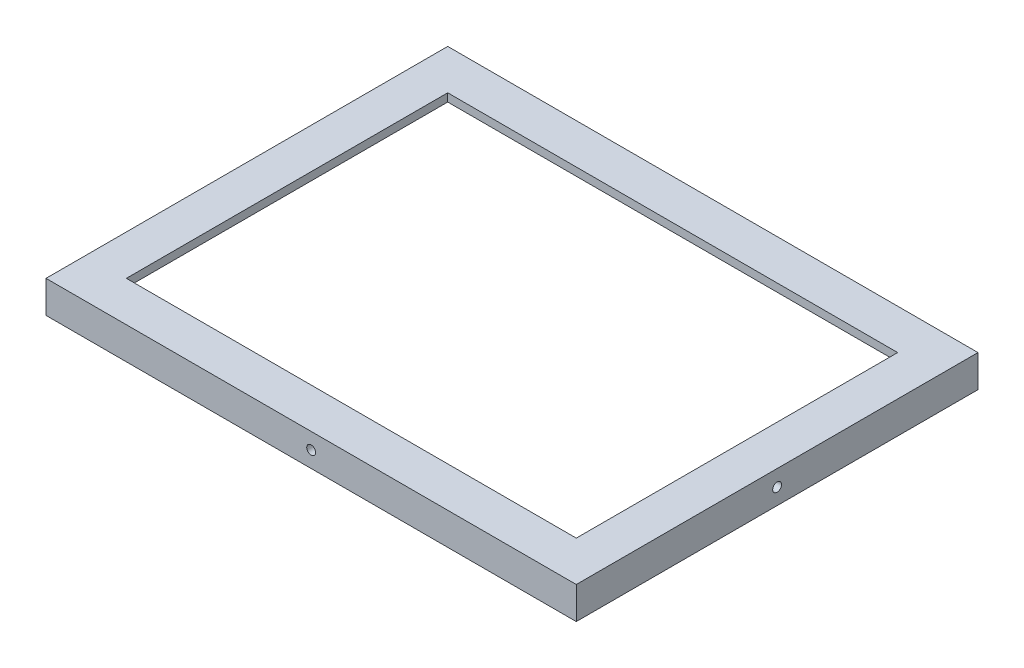
SolidWorks part; units mm, degrees
ref_plane "Front Plane" through (0, 0, 0) normal (0, 0, 1) x (1, 0, 0)
ref_plane "Top Plane" through (0, 0, 0) normal (0, 1, 0) x (1, 0, 0)
ref_plane "Right Plane" through (0, 0, 0) normal (1, 0, 0) x (0, 0, -1)
sketch "Sketch1" plane through (0, 9.525, 0) normal (0, 1, 0) x (1, 0, 0)
  line L12 (261.9455, 40.3596) -> (84.1455, 40.3596)
  line L13 (84.1455, 40.3596) -> (84.1455, -86.6404)
  line L14 (84.1455, -86.6404) -> (261.9455, -86.6404)
  line L15 (261.9455, -86.6404) -> (261.9455, 40.3596)
  line L16 (277.8205, 56.2346) -> (68.2705, 56.2346)
  line L17 (277.8205, -102.5154) -> (277.8205, 56.2346)
  line L18 (68.2705, -102.5154) -> (277.8205, -102.5154)
  line L19 (68.2705, 56.2346) -> (68.2705, -102.5154)
  line L20 (277.8205, 56.2346) -> (68.2705, 56.2346)
  line L21 (277.8205, -102.5154) -> (277.8205, 56.2346)
  line L22 (68.2705, -102.5154) -> (277.8205, -102.5154)
  line L23 (68.2705, 56.2346) -> (68.2705, -102.5154)
  dimension "D1" = 3.175
extrude "FrontFace" add sketch "Sketch1" along normal blind 3.175
sketch "Sketch3" plane through (0, 9.525, 0) normal (0, -1, 0) x (1, 0, 0)
  line L4 (277.8205, -56.2346) -> (277.8205, 102.5154)
  line L5 (277.8205, 102.5154) -> (68.2705, 102.5154)
  line L6 (68.2705, 102.5154) -> (68.2705, -56.2346)
  line L7 (68.2705, -56.2346) -> (277.8205, -56.2346)
  line L8 (277.8205, -56.2346) -> (277.8205, 102.5154)
  line L9 (277.8205, 102.5154) -> (68.2705, 102.5154)
  line L10 (68.2705, 102.5154) -> (68.2705, -56.2346)
  line L11 (68.2705, -56.2346) -> (277.8205, -56.2346)
  line L12 (71.1915, 99.5944) -> (71.1915, -53.3136)
  line L17 (71.1915, -53.3136) -> (274.8995, -53.3136)
  line L18 (274.8995, 99.5944) -> (274.8995, -53.3136)
  line L19 (71.1915, 99.5944) -> (274.8995, 99.5944)
  dimension "D1" = 0
extrude "SideShell" add sketch "Sketch3" along normal up to surface (9.525 mm away)
hole_wizard "#6-32 Tapped Hole1" positions "Sketch4" profile "Sketch5" tap size "#6-32" standard "ANSI Inch" end condition through all
sketch "Sketch4" plane through (277.8205, 0, 0) normal (1, 0, 0) x (0, 0, -1)
  line L2 (-102.5154, 12.7) -> (56.2346, 12.7) construction
  line L3 (-102.5154, 12.7) -> (-102.5154, 0) construction
  point P0 (-23.1404, 6.35)
  point P8 (-23.1404, 12.7)
  point P11 (-102.5154, 6.35)
sketch "Sketch5" plane through (277.8205, 6.35, 23.1404) normal (0, 1, 0) x (0, 0, -1)
  line L0 (0, 0) -> (0, 209.55)
  line L1 (0, 209.55) -> (1.7526, 209.55)
  line L2 (1.7526, 209.55) -> (1.7526, 0)
  line L5 (1.7526, 0) -> (0, 0)
  line L11 (0, -6.35) -> (0, 107.95) construction
  dimension "Thread Major Dia." = 3.5052
  dimension "Thru Tap Drill Depth" = 209.55
hole_wizard "#6-32 Tapped Hole2" positions "Sketch6" profile "Sketch7" tap size "#6-32" standard "ANSI Inch" end condition through all
sketch "Sketch6" plane through (0, 0, 102.5154) normal (0, 0, 1) x (1, 0, 0)
  line L0 (68.2705, 12.7) -> (277.8205, 12.7) construction
  line L1 (68.2705, 12.7) -> (68.2705, 0) construction
  point P0 (173.0455, 6.35)
  point P5 (173.0455, 12.7)
  point P8 (68.2705, 6.35)
sketch "Sketch7" plane through (173.0455, 6.35, 102.5154) normal (1, 0, 0) x (0, -1, 0)
  line L0 (0, 0) -> (0, 158.75)
  line L1 (0, 158.75) -> (1.7526, 158.75)
  line L2 (1.7526, 158.75) -> (1.7526, 0)
  line L5 (1.7526, 0) -> (0, 0)
  line L11 (0, -6.35) -> (0, 107.95) construction
  dimension "Thread Major Dia." = 3.5052
  dimension "Thru Tap Drill Depth" = 158.75
